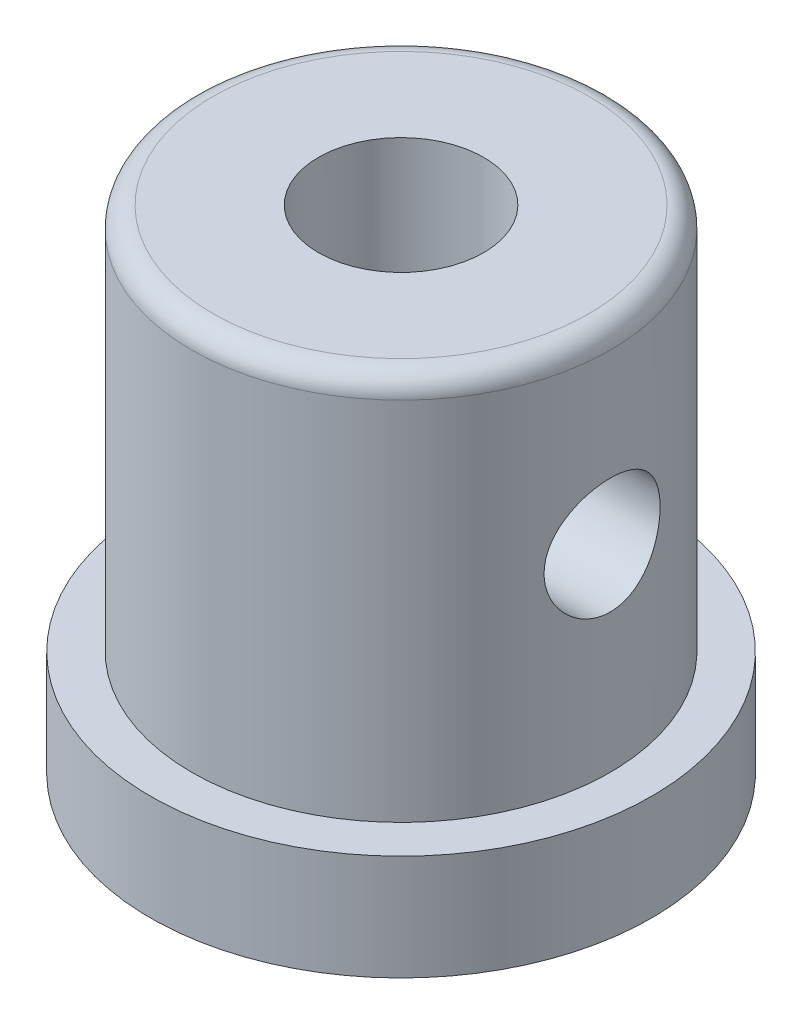
SolidWorks part; units mm, degrees
ref_plane "Front Plane" through (0, 0, 0) normal (0, 0, 1) x (1, 0, 0)
ref_plane "Top Plane" through (0, 0, 0) normal (0, 1, 0) x (1, 0, 0)
ref_plane "Right Plane" through (0, 0, 0) normal (1, 0, 0) x (0, 0, -1)
sketch "Sketch1" plane through (0, 0, 0) normal (0, 1, 0) x (1, 0, 0)
  circle A0 centre (0, 0) radius 9.05
  circle A1 centre (0, 0) radius 7.5565
  dimension "D1" = 18.1
  dimension "D2" = 15.113
extrude "Plate" add sketch "Sketch1" along normal blind 3.81 contours A1 | A0 A1 | A1 | A0 region at (-8.794, 0, 0) region at (0, 0, 0)
extrude "Plug" add sketch "Sketch1<3>" along normal blind 17.78 contours A1 region at (0, 0, 0)
sketch "Sketch1<3>" plane through (0, 0, 0) normal (0, 1, 0) x (1, 0, 0) same geometry as "Sketch1"
sketch "Sketch4" plane through (0, 0, 0) normal (1, 0, 0) x (0, 0, -1)
  line L0 (0, 10.922) -> (0, 0) construction
  line L1 (9.05, 3.81) -> (-9.05, 3.81) construction
  circle A0 centre (0, 10.922) radius 2.0955
  dimension "D1" = 7.112
  dimension "D2" = 4.191
extrude "Cut-Extrude1" cut sketch "Sketch4" against normal up to surface and the other way up to surface up to face at (0, 3.81, 7.5565) other way up to face at (0, 3.81, 7.5565)
fillet "Fillet1" radius 0.762 1 edges at (0, 17.78, 7.5565)
sketch "Sketch5" plane through (0, 17.78, 0) normal (0, 1, 0) x (1, 0, 0)
  circle A0 centre (0, 0) radius 2.9845
  dimension "D1" = 5.969
extrude "Cut-Extrude2" cut sketch "Sketch5" against normal up to next contours A0
